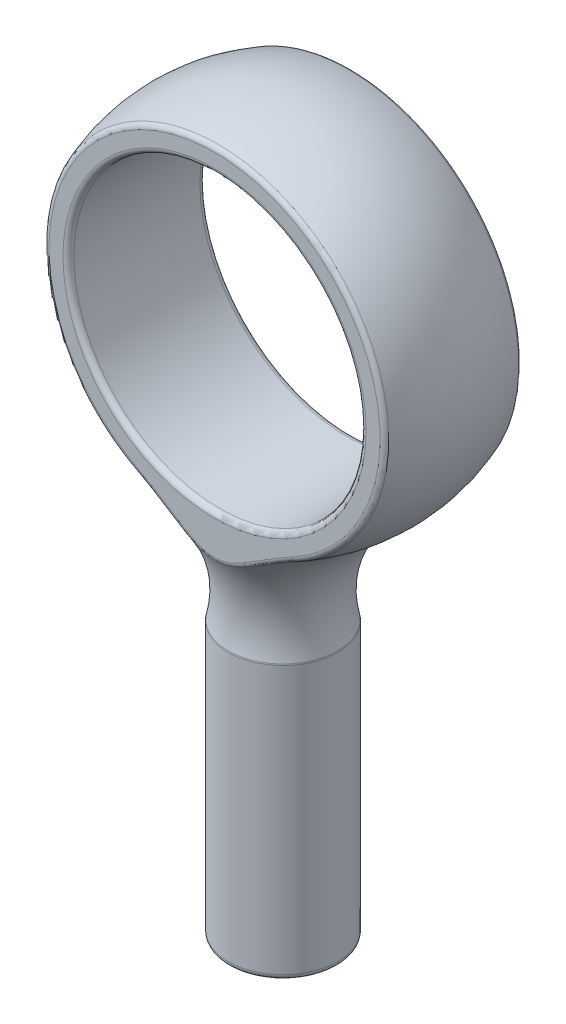
SolidWorks part; units mm, degrees
ref_plane "Front Plane" through (0, 0, 0) normal (0, 0, 1) x (1, 0, 0)
ref_plane "Top Plane" through (0, 0, 0) normal (0, 1, 0) x (1, 0, 0)
ref_plane "Right Plane" through (0, 0, 0) normal (1, 0, 0) x (0, 0, -1)
sketch "Sketch1" plane through (0, 0, 0) normal (0, 0, 1) x (1, 0, 0)
  line L0 (-1.5, -15) -> (-1.5, -7.5)
  line L1 (-1.5, -15) -> (1.5, -15)
  line L2 (1.5, -15) -> (1.5, -7.5)
  circle A0 centre (0, 0) radius 2 construction
  circle A1 centre (0, 0) radius 4
  circle A2 centre (0, 0) radius 5
  arc A3 (-1.5, -7.5) -> (-2.8075, -4.1374) centre (-4.5916, -6.7666) ccw
  arc A4 (1.5, -7.5) -> (2.8075, -4.1374) centre (4.5916, -6.7666) cw
  point P11 (0, 0)
  point P12 (0, 0)
  point P13 (0, 0)
  point P14 (0, -15)
  dimension "D1" = 10
  dimension "D2" = 8
  dimension "D3" = 4
  dimension "D4" = 15
  dimension "D5" = 3
  dimension "D6" = 7.5
sketch "Sketch2" plane through (0, 0, 0) normal (0, 0, 1) x (1, 0, 0)
  line L0 (0, 5) -> (0, -15)
  line L1 (-1.5, -15) -> (1.5, -15) construction
  line L2 (-1.5, -15) -> (-1.5, -7.5) construction
  line L3 (-1.5, -15) -> (0, -15)
  line L4 (-1.5, -15) -> (-1.5, -7.5)
  circle A0 centre (0, 0) radius 5 construction
  arc A1 (-1.5, -7.5) -> (-2.8075, -4.1374) centre (-4.5916, -6.7666) ccw construction
  arc A2 (-1.5, -7.5) -> (-2.8075, -4.1374) centre (-4.5916, -6.7666) ccw
  arc A3 (0, 5) -> (-2.8075, -4.1374) centre (0, 0) ccw
revolve "Revolve1" add sketch "Sketch2" angle 360 about L0
sketch "Sketch3" plane through (0, 0, 0) normal (1, 0, 0) x (0, 0, -1)
  line L0 (10.828, -19.6155) -> (10.828, 7.6637)
  line L1 (10.828, 7.6637) -> (1.875, 7.6637)
  line L2 (1.875, 7.6637) -> (1.875, -5.2528)
  line L3 (2.7792, -8.1207) -> (10.828, -19.6155)
  line L4 (0, 0) -> (0, 16.9001) construction
  line L5 (-2.7792, -8.1207) -> (-10.828, -19.6155)
  line L6 (-1.875, 7.6637) -> (-1.875, -5.2528)
  line L7 (-10.828, 7.6637) -> (-1.875, 7.6637)
  line L8 (-10.828, -19.6155) -> (-10.828, 7.6637)
  arc A0 (1.875, -5.2528) -> (2.7792, -8.1207) centre (6.875, -5.2528) ccw
  arc A1 (-1.875, -5.2528) -> (-2.7792, -8.1207) centre (-6.875, -5.2528) cw
  point P7 (0, 0)
  point P16 (6.875, -19.1043)
  point P17 (11.2463, 7.6637)
  point P18 (10.8745, -19.8014)
  point P19 (10.828, -19.6155)
  dimension "D1" = 5
  dimension "D2" = 145
  dimension "D3" = 3.75
extrude "Cut-Extrude1" cut sketch "Sketch3" against normal blind 10 and the other way blind 10
sketch "Sketch4" plane through (0, 0, -1.875) normal (0, 0, -1) x (-1, 0, 0)
  circle A0 centre (0, 0) radius 4 construction
  circle A1 centre (0, 0) radius 4
extrude "Cut-Extrude2" cut sketch "Sketch4" against normal blind 10 and the other way blind 10
fillet "Fillet1" radius 0.15 8 edges at (4, 0, 1.875) (-4, 0, -1.875) (0, 4.6351, 1.875) (0, 4.6351, -1.875) (0, -15, 1.5) (0, -7.5, 1.5) (-0.1402, -8.4232, 1.875) (0.1402, -8.4232, -1.875)
sketch "Sketch5" plane through (0, -15, 0) normal (0, -1, 0) x (1, 0, 0)
  circle A0 centre (0, 0) radius 1
  dimension "D1" = 2
extrude "Cut-Extrude3" cut sketch "Sketch5" against normal blind 5
chamfer "Chamfer1" distance 0.05 angle 45 1 edges at (0, -15, -1)
